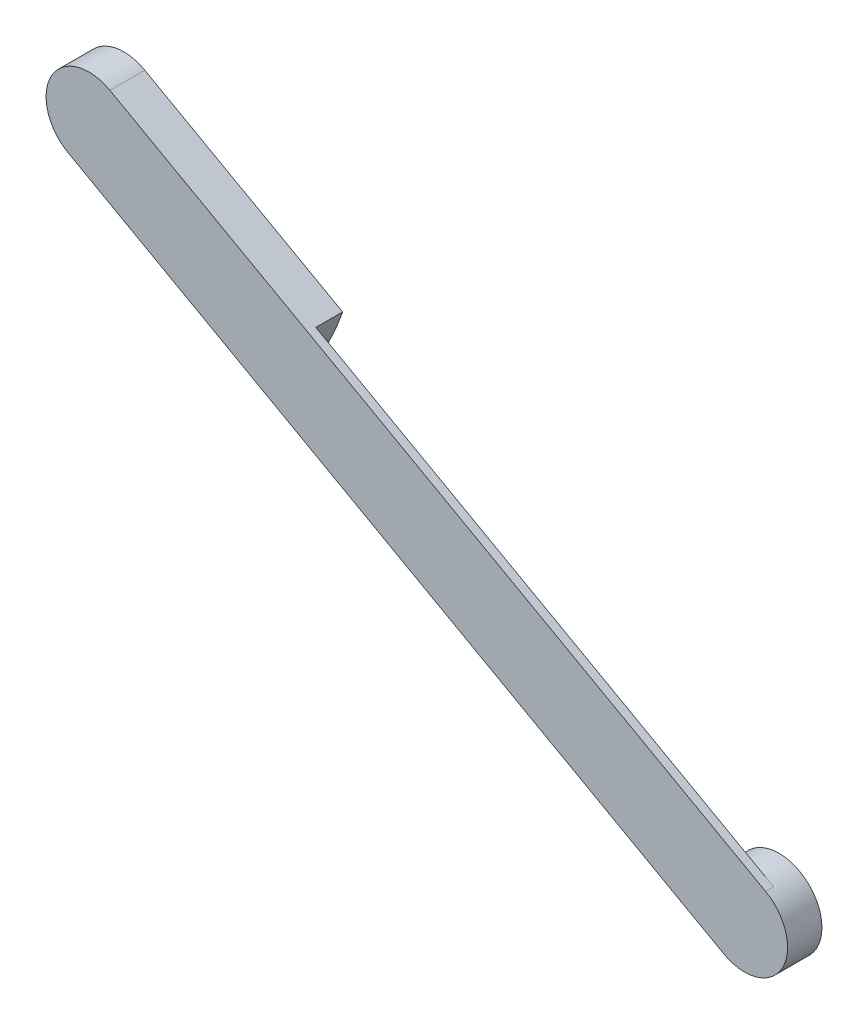
SolidWorks part; units mm, degrees
ref_plane "Plan de face" through (0, 0, 0) normal (0, 0, 1) x (1, 0, 0)
ref_plane "Plan de dessus" through (0, 0, 0) normal (0, 1, 0) x (1, 0, 0)
ref_plane "Plan de droite" through (0, 0, 0) normal (1, 0, 0) x (0, 0, -1)
sketch "Esquisse1" plane through (0, 0, 0) normal (0, 0, 1) x (1, 0, 0)
  line L0 (-5.7517, -9.8772) -> (-6.8338, -9.7825) construction
  line L1 (-6.8338, -9.7825) -> (-6.9494, -9.1264) construction
  line L2 (-6.9494, -9.1264) -> (-5.9535, -8.662) construction
  line L3 (-6.0657, -8.3442) -> (-7.1383, -8.6316) construction
  line L4 (-7.1383, -8.6316) -> (-7.4714, -8.0546) construction
  line L5 (-7.4714, -8.0546) -> (-6.6788, -7.262) construction
  line L6 (-6.8912, -7.0053) -> (-7.818, -7.6542) construction
  line L7 (-7.818, -7.6542) -> (-8.3284, -7.226) construction
  line L8 (-8.3284, -7.226) -> (-7.8476, -6.1949) construction
  line L9 (-8.1333, -6.0289) -> (-8.7911, -6.9683) construction
  line L10 (-8.7911, -6.9683) -> (-9.4172, -6.7405) construction
  line L11 (-9.4172, -6.7405) -> (-9.3172, -5.5977) construction
  line L12 (-9.6413, -5.5414) -> (-9.9401, -6.6566) construction
  line L13 (-9.9401, -6.6566) -> (-10.6064, -6.6566) construction
  line L14 (-10.6064, -6.6566) -> (-10.9035, -5.5477) construction
  line L15 (-11.227, -5.6073) -> (-11.1264, -6.7566) construction
  line L16 (-11.1264, -6.7566) -> (-11.7525, -6.9845) construction
  line L17 (-11.7525, -6.9845) -> (-12.4065, -6.0504) construction
  line L18 (-12.6906, -6.2193) -> (-12.207, -7.2564) construction
  line L19 (-12.207, -7.2564) -> (-12.7173, -7.6846) construction
  line L20 (-12.7173, -7.6846) -> (-13.6389, -7.0393) construction
  line L21 (-13.8487, -7.2983) -> (-13.0514, -8.0955) construction
  line L22 (-13.0514, -8.0955) -> (-13.3846, -8.6725) construction
  line L23 (-13.3846, -8.6725) -> (-14.4509, -8.3868) construction
  line L24 (-14.5599, -8.7057) -> (-13.558, -9.1729) construction
  line L25 (-13.558, -9.1729) -> (-13.6737, -9.8291) construction
  line L26 (-13.6737, -9.8291) -> (-14.7493, -9.9232) construction
  line L27 (-14.7422, -10.2644) -> (-13.6655, -10.3586) construction
  line L28 (-13.6655, -10.3586) -> (-13.5498, -11.0147) construction
  line L29 (-13.5498, -11.0147) -> (-14.5063, -11.4608) construction
  line L30 (-14.3817, -11.783) -> (-13.3609, -11.5095) construction
  line L31 (-13.3609, -11.5095) -> (-13.0278, -12.0865) construction
  line L32 (-13.0278, -12.0865) -> (-13.7588, -12.8175) construction
  line L33 (-13.5298, -13.0811) -> (-12.6812, -12.4869) construction
  line L34 (-12.6812, -12.4869) -> (-12.1708, -12.9151) construction
  line L35 (-12.1708, -12.9151) -> (-12.6007, -13.8372) construction
  line L36 (-12.2937, -14.0091) -> (-11.7081, -13.1728) construction
  line L37 (-11.7081, -13.1728) -> (-11.082, -13.4007) construction
  line L38 (-11.082, -13.4007) -> (-11.1699, -14.405) construction
  line L39 (-10.8214, -14.4636) -> (-10.5591, -13.4845) construction
  line L40 (-10.5591, -13.4845) -> (-9.8929, -13.4845) construction
  line L41 (-9.8929, -13.4845) -> (-9.6322, -14.4574) construction
  line L42 (-9.2844, -14.3952) -> (-9.3728, -13.3845) construction
  line L43 (-9.3728, -13.3845) -> (-8.7467, -13.1566) construction
  line L44 (-8.7467, -13.1566) -> (-8.1648, -13.9877) construction
  line L45 (-7.8596, -13.8126) -> (-8.2922, -12.8848) construction
  line L46 (-8.2922, -12.8848) -> (-7.7819, -12.4565) construction
  line L47 (-7.7819, -12.4565) -> (-6.9385, -13.047) construction
  line L48 (-6.7123, -12.7811) -> (-7.4478, -12.0456) construction
  line L49 (-7.4478, -12.0456) -> (-7.1146, -11.4686) construction
  line L50 (-7.1146, -11.4686) -> (-6.1002, -11.7404) construction
  line L51 (-5.9789, -11.4169) -> (-6.9412, -10.9682) construction
  line L52 (-6.9412, -10.9682) -> (-6.8255, -10.3121) construction
  line L53 (-6.8255, -10.3121) -> (-5.7553, -10.2184) construction
  line L54 (-5.7517, -9.8772) -> (-6.8338, -9.7825)
  line L55 (-6.8338, -9.7825) -> (-6.9494, -9.1264)
  line L56 (-6.9494, -9.1264) -> (-5.9535, -8.662)
  line L57 (-6.0657, -8.3442) -> (-7.1383, -8.6316)
  line L58 (-7.1383, -8.6316) -> (-7.4714, -8.0546)
  line L59 (-7.4714, -8.0546) -> (-6.6788, -7.262)
  line L60 (-6.8912, -7.0053) -> (-7.818, -7.6542)
  line L61 (-7.818, -7.6542) -> (-8.3284, -7.226)
  line L62 (-8.3284, -7.226) -> (-7.8476, -6.1949)
  line L63 (-8.1333, -6.0289) -> (-8.7911, -6.9683)
  line L64 (-8.7911, -6.9683) -> (-9.4172, -6.7405)
  line L65 (-9.4172, -6.7405) -> (-9.3172, -5.5977)
  line L66 (-9.6413, -5.5414) -> (-9.9401, -6.6566)
  line L67 (-9.9401, -6.6566) -> (-10.6064, -6.6566)
  line L68 (-10.6064, -6.6566) -> (-10.9035, -5.5477)
  line L69 (-11.227, -5.6073) -> (-11.1264, -6.7566)
  line L70 (-11.1264, -6.7566) -> (-11.7525, -6.9845)
  line L71 (-11.7525, -6.9845) -> (-12.4065, -6.0504)
  line L72 (-12.6906, -6.2193) -> (-12.207, -7.2564)
  line L73 (-12.207, -7.2564) -> (-12.7173, -7.6846)
  line L74 (-12.7173, -7.6846) -> (-13.6389, -7.0393)
  line L75 (-13.8487, -7.2983) -> (-13.0514, -8.0955)
  line L76 (-13.0514, -8.0955) -> (-13.3846, -8.6725)
  line L77 (-13.3846, -8.6725) -> (-14.4509, -8.3868)
  line L78 (-14.5599, -8.7057) -> (-13.558, -9.1729)
  line L79 (-13.558, -9.1729) -> (-13.6737, -9.8291)
  line L80 (-13.6737, -9.8291) -> (-14.7493, -9.9232)
  line L81 (-14.7422, -10.2644) -> (-13.6655, -10.3586)
  line L82 (-13.6655, -10.3586) -> (-13.5498, -11.0147)
  line L83 (-13.5498, -11.0147) -> (-14.5063, -11.4608)
  line L84 (-14.3817, -11.783) -> (-13.3609, -11.5095)
  line L85 (-13.3609, -11.5095) -> (-13.0278, -12.0865)
  line L86 (-13.0278, -12.0865) -> (-13.7588, -12.8175)
  line L87 (-13.5298, -13.0811) -> (-12.6812, -12.4869)
  line L88 (-12.6812, -12.4869) -> (-12.1708, -12.9151)
  line L89 (-12.1708, -12.9151) -> (-12.6007, -13.8372)
  line L90 (-12.2937, -14.0091) -> (-11.7081, -13.1728)
  line L91 (-11.7081, -13.1728) -> (-11.082, -13.4007)
  line L92 (-11.082, -13.4007) -> (-11.1699, -14.405)
  line L93 (-10.8214, -14.4636) -> (-10.5591, -13.4845)
  line L94 (-10.5591, -13.4845) -> (-9.8929, -13.4845)
  line L95 (-9.8929, -13.4845) -> (-9.6322, -14.4574)
  line L96 (-9.2844, -14.3952) -> (-9.3728, -13.3845)
  line L97 (-9.3728, -13.3845) -> (-8.7467, -13.1566)
  line L98 (-8.7467, -13.1566) -> (-8.1648, -13.9877)
  line L99 (-7.8596, -13.8126) -> (-8.2922, -12.8848)
  line L100 (-8.2922, -12.8848) -> (-7.7819, -12.4565)
  line L101 (-7.7819, -12.4565) -> (-6.9385, -13.047)
  line L102 (-6.7123, -12.7811) -> (-7.4478, -12.0456)
  line L103 (-7.4478, -12.0456) -> (-7.1146, -11.4686)
  line L104 (-7.1146, -11.4686) -> (-6.1002, -11.7404)
  line L105 (-5.9789, -11.4169) -> (-6.9412, -10.9682)
  line L106 (-6.9412, -10.9682) -> (-6.8255, -10.3121)
  line L107 (-6.8255, -10.3121) -> (-5.7553, -10.2184)
  circle A0 centre (-10.25, -10) radius 8 construction
  arc A1 (-5.9535, -8.662) -> (-6.0657, -8.3442) centre (-10.25, -10) ccw construction
  arc A2 (-6.6788, -7.262) -> (-6.8912, -7.0053) centre (-10.25, -10) ccw construction
  arc A3 (-7.8476, -6.1949) -> (-8.1333, -6.0289) centre (-10.25, -10) ccw construction
  arc A4 (-9.3172, -5.5977) -> (-9.6413, -5.5414) centre (-10.25, -10) ccw construction
  arc A5 (-10.9035, -5.5477) -> (-11.227, -5.6073) centre (-10.25, -10) ccw construction
  arc A6 (-12.4065, -6.0504) -> (-12.6906, -6.2193) centre (-10.25, -10) ccw construction
  arc A7 (-13.6389, -7.0393) -> (-13.8487, -7.2983) centre (-10.25, -10) ccw construction
  arc A8 (-14.4509, -8.3868) -> (-14.5599, -8.7057) centre (-10.25, -10) ccw construction
  arc A9 (-14.7493, -9.9232) -> (-14.7422, -10.2644) centre (-10.25, -10) ccw construction
  arc A10 (-14.5063, -11.4608) -> (-14.3817, -11.783) centre (-10.25, -10) ccw construction
  arc A11 (-13.7588, -12.8175) -> (-13.5298, -13.0811) centre (-10.25, -10) ccw construction
  arc A12 (-12.6007, -13.8372) -> (-12.2937, -14.0091) centre (-10.25, -10) ccw construction
  arc A13 (-11.1699, -14.405) -> (-10.8214, -14.4636) centre (-10.25, -10) ccw construction
  arc A14 (-9.6322, -14.4574) -> (-9.2844, -14.3952) centre (-10.25, -10) ccw construction
  arc A15 (-8.1648, -13.9877) -> (-7.8596, -13.8126) centre (-10.25, -10) ccw construction
  arc A16 (-6.9385, -13.047) -> (-6.7123, -12.7811) centre (-10.25, -10) ccw construction
  arc A17 (-6.1002, -11.7404) -> (-5.9789, -11.4169) centre (-10.25, -10) ccw construction
  arc A18 (-5.7553, -10.2184) -> (-5.7517, -9.8772) centre (-10.25, -10) ccw construction
  circle A19 centre (-10.25, -10) radius 8
  arc A20 (-5.9535, -8.662) -> (-6.0657, -8.3442) centre (-10.25, -10) ccw
  arc A21 (-6.6788, -7.262) -> (-6.8912, -7.0053) centre (-10.25, -10) ccw
  arc A22 (-7.8476, -6.1949) -> (-8.1333, -6.0289) centre (-10.25, -10) ccw
  arc A23 (-9.3172, -5.5977) -> (-9.6413, -5.5414) centre (-10.25, -10) ccw
  arc A24 (-10.9035, -5.5477) -> (-11.227, -5.6073) centre (-10.25, -10) ccw
  arc A25 (-12.4065, -6.0504) -> (-12.6906, -6.2193) centre (-10.25, -10) ccw
  arc A26 (-13.6389, -7.0393) -> (-13.8487, -7.2983) centre (-10.25, -10) ccw
  arc A27 (-14.4509, -8.3868) -> (-14.5599, -8.7057) centre (-10.25, -10) ccw
  arc A28 (-14.7493, -9.9232) -> (-14.7422, -10.2644) centre (-10.25, -10) ccw
  arc A29 (-14.5063, -11.4608) -> (-14.3817, -11.783) centre (-10.25, -10) ccw
  arc A30 (-13.7588, -12.8175) -> (-13.5298, -13.0811) centre (-10.25, -10) ccw
  arc A31 (-12.6007, -13.8372) -> (-12.2937, -14.0091) centre (-10.25, -10) ccw
  arc A32 (-11.1699, -14.405) -> (-10.8214, -14.4636) centre (-10.25, -10) ccw
  arc A33 (-9.6322, -14.4574) -> (-9.2844, -14.3952) centre (-10.25, -10) ccw
  arc A34 (-8.1648, -13.9877) -> (-7.8596, -13.8126) centre (-10.25, -10) ccw
  arc A35 (-6.9385, -13.047) -> (-6.7123, -12.7811) centre (-10.25, -10) ccw
  arc A36 (-6.1002, -11.7404) -> (-5.9789, -11.4169) centre (-10.25, -10) ccw
  arc A37 (-5.7553, -10.2184) -> (-5.7517, -9.8772) centre (-10.25, -10) ccw
extrude "Boss.-Extru.1" add sketch "Esquisse1" against normal blind 4.9
sketch "Esquisse2" plane through (0, 0, 0) normal (0, 0, 1) x (1, 0, 0)
  line L1 (-14.1487, -16.9857) -> (-136.3988, 51.2411)
  line L2 (-128.6015, 65.2125) -> (-6.3513, -3.0143)
  arc A0 (-128.6015, 65.2125) -> (-136.3988, 51.2411) centre (-132.5002, 58.2268) ccw
  circle A1 centre (-10.25, -10) radius 8
  arc A2 (-14.1487, -16.9857) -> (-6.3513, -3.0143) centre (-10.25, -10) ccw
  dimension "D2" = 140
  dimension "D1" = 0
extrude "Boss.-Extru.2" add sketch "Esquisse2" along normal blind 1.5
sketch "Esquisse3" plane through (0, 0, 0) normal (0, 0, -1) x (-1, 0, 0)
  line L0 (128.6015, 65.2125) -> (91.7088, 44.623)
  line L1 (6.3513, -3.0143) -> (128.6015, 65.2125) construction
  line L2 (14.1487, -16.9857) -> (136.3988, 51.2411)
  line L3 (128.6015, 65.2125) -> (6.3513, -3.0143)
  line L5 (136.3988, 51.2411) -> (99.5061, 30.6516)
  line L6 (136.3988, 51.2411) -> (14.1487, -16.9857) construction
  arc A0 (136.3988, 51.2411) -> (128.6015, 65.2125) centre (132.5002, 58.2268) ccw
  arc A1 (91.7088, 44.623) -> (99.5061, 30.6516) centre (132.5002, 58.2268) ccw
  arc A2 (14.1487, -16.9857) -> (6.3513, -3.0143) centre (10.25, -10) ccw
  arc A3 (136.3988, 51.2411) -> (128.6015, 65.2125) centre (132.5002, 58.2268) ccw
  arc A5 (136.3988, 51.2411) -> (128.6015, 65.2125) centre (132.5002, 58.2268) ccw
  circle A7 centre (132.5002, 58.2268) radius 43 construction
  circle A8 centre (132.5002, 58.2268) radius 8 construction
  point P8 (140.1506, 60.5658)
  point P12 (175.5002, 58.2268)
  line M10 (14.1487, -16.9857) -> (136.3988, 51.2411)
  arc M11 (136.3988, 51.2411) -> (128.6015, 65.2125) centre (132.5002, 58.2268) ccw
  line M12 (128.6015, 65.2125) -> (6.3513, -3.0143)
  dimension "D1" = 0
  dimension "D2" = 35
extrude "Boss.-Extru.3" add sketch "Esquisse3" along normal blind 5 contours A1 M12 M10 M11 region at (-116.6061, 49.3565, 0)
